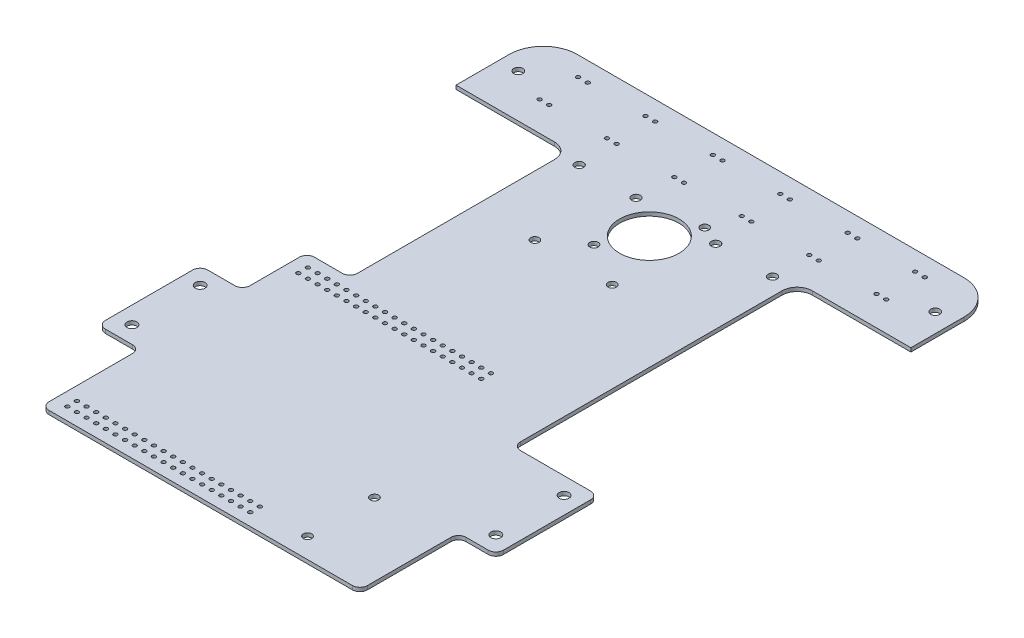
SolidWorks part; units mm, degrees
material "Thornel VCB-20 Carbon Cloth"
ref_plane "Front" through (0, 0, 0) normal (0, 0, 1) x (1, 0, 0)
ref_plane "Top" through (0, 0, 0) normal (0, 1, 0) x (1, 0, 0)
ref_plane "Right" through (0, 0, 0) normal (1, 0, 0) x (0, 0, -1)
ref_axis "X" through (-80.9, 0, 0) along (1, 0, 0)
ref_axis "Y" through (0, -50, 0) along (0, 1, 0)
ref_axis "Z" through (0, 0, -80.9) along (0, 0, 1)
sketch "Sketch1" plane through (0, 0, 0) normal (0, 1, 0) x (1, 0, 0)
  line L0 (-52.5, -125) -> (-41.35, -125)
  line L1 (-52.5, -125) -> (-52.5, -98)
  line L2 (-52.5, -98) -> (-41.35, -98)
  line L3 (-30, -81) -> (-30, -23)
  line L4 (-30, -23) -> (-60, -23)
  line L5 (-60, -23) -> (-60, 0)
  line L6 (-60, 0) -> (60, 0)
  line L7 (60, 0) -> (60, -23)
  line L8 (60, -23) -> (30, -23)
  line L9 (30, -23) -> (30, -98)
  line L10 (30, -98) -> (52.5, -98)
  line L11 (52.5, -98) -> (52.5, -125)
  line L12 (0, -162) -> (0, 0) construction
  line L13 (-41.35, -125) -> (-41.35, -151)
  line L14 (-41.35, -151) -> (42.65, -151)
  line L15 (42.65, -151) -> (42.65, -125)
  line L16 (42.65, -125) -> (52.5, -125)
  line L18 (-41.35, -98) -> (-41.35, -81)
  line L19 (-41.35, -81) -> (-30, -81)
  dimension "D1" = 105
  dimension "D2" = 60
  dimension "D3" = 27
  dimension "D4" = 90
  dimension "D5" = 23
  dimension "D6" = 120
  dimension "D7" = 125
  dimension "D8" = 41.35
  dimension "D9" = 26
  dimension "D10" = 42.65
  dimension "D11" = 17
extrude "Boss-Extrude1" add sketch "Sketch1" along normal mid plane 1
hole_wizard "M2 Clearance Hole1" positions "Sketch2" profile "Sketch3" hole size "M2" standard "ANSI Metric" end condition up to next
sketch "Sketch2" plane through (0, 0.5, 0) normal (0, 1, 0) x (1, 0, 0)
  line L0 (-48, -120.5) -> (48, -120.5) construction
  line L2 (-52.5, -125) -> (-41.35, -125) construction
  line L3 (-52.5, -98) -> (-52.5, -125) construction
  line L4 (52.5, -125) -> (52.5, -98) construction
  line L5 (-48, -102.5) -> (-48, -120.5) construction
  line L8 (48, -102.5) -> (48, -120.5) construction
  point P0 (-48, -120.5)
  point P2 (48, -120.5)
  point P15 (-48, -102.5)
  point P17 (48, -102.5)
  dimension "D1" = 4.5
  dimension "D2" = 4.5
  dimension "D3" = 4.5
  dimension "D4" = 18
sketch "Sketch3" plane through (-48, 0.5, 120.5) normal (1, 0, 0) x (0, 0, 1)
  line L0 (0, 0) -> (0, 1)
  line L1 (0, 1) -> (1.3, 1)
  line L2 (1.3, 1) -> (1.3, 0)
  line L5 (1.3, 0) -> (0, 0)
  line L11 (0, -6.35) -> (0, 107.95) construction
  dimension "Thru Hole Dia." = 2.6
  dimension "Thru Hole Depth" = 1
fillet "Fillet1" radius 2 7 edges at (-52.5, 0, 125) (52.5, 0, 98) (-52.5, 0, 98) (-41.35, 0, 151) (42.65, 0, 151) (52.5, 0, 125) (-41.35, 0, 81)
fillet "Fillet2" radius 9 2 edges at (60, 0, 0) (-60, 0, 0)
hole_wizard "M2 Clearance Hole2" positions "Sketch7" profile "Sketch8" hole size "M2" standard "ANSI Metric" end condition up to next
sketch "Sketch7" plane through (0, 0.5, 0) normal (0, 1, 0) x (1, 0, 0)
  line L0 (-55, -11.57) -> (55, -11.57) construction
  line L2 (0, 0) -> (0, -11.57) construction
  line L3 (51, 0) -> (-51, 0) construction
  line L5 (-60, -23) -> (-30, -23) construction
  point P0 (-55, -11.57)
  point P2 (55, -11.57)
  dimension "D1" = 110
  dimension "D2" = 11.43
sketch "Sketch8" plane through (-55, 0.5, 11.57) normal (1, 0, 0) x (0, 0, 1)
  line L0 (0, 0) -> (0, 1)
  line L1 (0, 1) -> (1.2, 1)
  line L2 (1.2, 1) -> (1.2, 0)
  line L5 (1.2, 0) -> (0, 0)
  line L11 (0, -6.35) -> (0, 107.95) construction
  dimension "Thru Hole Dia." = 2.4
  dimension "Thru Hole Depth" = 1
fillet "Fillet4" radius 2 5 edges at (30, 0, 98) (42.65, 0, 125) (-41.35, 0, 125) (-30, 0, 81) (-41.35, 0, 98)
fillet "Fillet5" radius 4 2 edges at (30, 0, 23) (-30, 0, 23)
sketch "Sketch13" plane through (0, 0.5, 0) normal (0, 1, 0) x (1, 0, 0)
  line L0 (-38, -106) -> (-38, -117) construction
  line L1 (-35, -106) -> (-35, -117)
  line L3 (38, -106) -> (38, -117) construction
  line L5 (35, -106) -> (35, -117)
  line L6 (-38, -111.5) -> (38, -111.5) construction
  line L7 (0, -111.5) -> (0, 0) construction
  line L8 (51, 0) -> (-51, 0) construction
  line L11 (-48, -102.5) -> (-48, -120.5) construction
  line L12 (-48, -111.5) -> (-38, -111.5) construction
  line L13 (-38, -103) -> (-45.5, -103)
  line L14 (-38, -120) -> (-45.5, -120)
  line L15 (38, -103) -> (45.5, -103)
  line L16 (38, -120) -> (45.5, -120)
  line L17 (48.5, -106) -> (48.5, -117)
  line L18 (-48.5, -106) -> (-48.5, -117)
  line L19 (-35, -111.5) -> (-48.5, -111.5) construction
  line L20 (35, -111.5) -> (48.5, -111.5) construction
  arc A0 (-35, -106) -> (-38, -103) centre (-38, -106) ccw
  arc A1 (-38, -120) -> (-35, -117) centre (-38, -117) ccw
  arc A2 (38, -103) -> (35, -106) centre (38, -106) ccw
  arc A3 (35, -117) -> (38, -120) centre (38, -117) ccw
  circle A4 centre (-48, -102.5) radius 1.3 construction
  arc A5 (45.5, -103) -> (48.5, -106) centre (45.5, -106) cw
  arc A6 (48.5, -117) -> (45.5, -120) centre (45.5, -117) cw
  arc A7 (-45.5, -103) -> (-48.5, -106) centre (-45.5, -106) ccw
  arc A8 (-48.5, -117) -> (-45.5, -120) centre (-45.5, -117) ccw
  point P2 (-38, -111.5)
  point P8 (38, -111.5)
  dimension "D5" = 3.5
  dimension "D1" = 17
  dimension "D2" = 13.5
  dimension "D3" = 70
extrude "Cut-Extrude4" [suppressed] cut sketch "Sketch13" against normal through all
hole_wizard "M2 Clearance Hole3" positions "Sketch14" profile "Sketch15" hole size "M2" standard "ANSI Metric" end condition up to next
sketch "Sketch14" plane through (0, 0.5, 0) normal (0, 1, 0) x (1, 0, 0)
  line L2 (5.35, -22.7335) -> (-5.35, -41.2665) construction
  line L3 (0, 0) -> (0, -32) construction
  line L4 (51, 0) -> (-51, 0) construction
  point P0 (5.35, -22.7335)
  point P2 (-5.35, -41.2665)
  dimension "D1" = 21.4
  dimension "D2" = 32
  dimension "D3" = 30
sketch "Sketch15" plane through (5.35, 0.5, 22.7335) normal (1, 0, 0) x (0, 0, 1)
  line L0 (0, 0) -> (0, 1)
  line L1 (0, 1) -> (1.1, 1)
  line L2 (1.1, 1) -> (1.1, 0)
  line L5 (1.1, 0) -> (0, 0)
  line L11 (0, -6.35) -> (0, 107.95) construction
  dimension "Thru Hole Dia." = 2.2
  dimension "Thru Hole Depth" = 1
sketch "Sketch17" plane through (0, 0.5, 0) normal (0, 1, 0) x (1, 0, 0)
  line L0 (-25.5, -25) -> (-10.5, -25) construction
  line L1 (-10.5, -25) -> (10.5, -25) construction
  line L2 (10.5, -25) -> (25.5, -25) construction
  line L4 (0, -25) -> (0, 0) construction
  line L5 (-18, -25) -> (-18, -29.652) construction
  line L7 (51, 0) -> (-51, 0) construction
  line L8 (18, -25) -> (18, -28.4507) construction
  circle A8 centre (25.5, -25) radius 1.15
  circle A9 centre (10.5, -25) radius 1.15
  circle A10 centre (-10.5, -25) radius 1.15
  circle A11 centre (-25.5, -25) radius 1.15
  dimension "D7" = 2.3
  dimension "D1" = 15
  dimension "D2" = 36
  dimension "D4" = 25
extrude "Cut-Extrude6" cut sketch "Sketch17" against normal through all
sketch "Sketch18" plane through (0, 0.5, 0) normal (0, 1, 0) x (1, 0, 0)
  line L0 (5.35, -22.7335) -> (-5.35, -41.2665) construction
  circle A0 centre (0, -32) radius 7.85
  circle A6 centre (5.35, -22.7335) radius 1.1 construction
  circle A8 centre (-5.35, -41.2665) radius 1.1 construction
  dimension "D3" = 15.7
extrude "Cut-Extrude7" cut sketch "Sketch18" against normal up to next
hole_wizard "M2 Clearance Hole4" positions "Sketch19" profile "Sketch20" hole size "M2" standard "ANSI Metric" end condition up to next
sketch "Sketch19" plane through (0, 0.5, 0) normal (0, 1, 0) x (1, 0, 0)
  line L0 (-14.21, -48) -> (6.21, -48) construction
  line L2 (0, 0) -> (0, -48) construction
  line L3 (51, 0) -> (-51, 0) construction
  point P0 (-14.21, -48)
  point P2 (6.21, -48)
  dimension "D1" = 20.42
  dimension "D2" = 6.21
  dimension "D3" = 48
sketch "Sketch20" plane through (-14.21, 0.5, 48) normal (1, 0, 0) x (0, 0, 1)
  line L0 (0, 0) -> (0, 1)
  line L1 (0, 1) -> (1.1, 1)
  line L2 (1.1, 1) -> (1.1, 0)
  line L5 (1.1, 0) -> (0, 0)
  line L11 (0, -6.35) -> (0, 107.95) construction
  dimension "Thru Hole Dia." = 2.2
  dimension "Thru Hole Depth" = 1
sketch "Sketch21" plane through (0, 0.5, 0) normal (0, 1, 0) x (1, 0, 0)
  line L0 (-37.826, -86.7798) -> (-37.826, -147.73) construction
  line L4 (-39.35, -151) -> (40.65, -151) construction
  line L5 (-41.35, -127) -> (-41.35, -149) construction
  circle A0 centre (-37.826, -147.73) radius 0.51
  circle A2 centre (-37.826, -86.7798) radius 0.51
  dimension "D2" = 1.02
  dimension "D3" = 3.524
  dimension "D4" = 3.27
  dimension "D1" = 60.9502
extrude "Cut-Extrude8" cut sketch "Sketch21" against normal up to next
pattern_linear "LPattern1" count 2 spacing 2.54 along (0, 0, -1) count 20 spacing 2.54 along (1, 0, 0) of "Cut-Extrude8"
sketch "Sketch22" plane through (0, 0.5, 0) normal (0, 1, 0) x (1, 0, 0)
  line L0 (-45.72, -5.08) -> (-43.18, -5.08) construction
  line L1 (51, 0) -> (-51, 0) construction
  line L2 (-44.45, -5.08) -> (-44.45, 0) construction
  circle A0 centre (-45.72, -5.08) radius 0.51
  circle A1 centre (-43.18, -5.08) radius 0.51
  point P8 (0, 0)
  dimension "D2" = 1.02
  dimension "D1" = 2.54
  dimension "D3" = 5.08
  dimension "D4" = 44.45
extrude "Cut-Extrude9" cut sketch "Sketch22" against normal up to next
pattern_linear "LPattern2" count 2 spacing 10.16 along (0, 0, 1) count 6 spacing 17.78 along (1, 0, 0) of "Cut-Extrude9"
sketch "Sketch23" plane through (0, 0.5, 0) normal (0, 1, 0) x (1, 0, 0)
  line L0 (42.65, -149) -> (42.65, -127) construction
  line L1 (-39.35, -151) -> (40.65, -151) construction
  circle A0 centre (23.48, -145.65) radius 1.1
  circle A1 centre (23.48, -128) radius 1.1
  point P4 (0, 0)
  dimension "D1" = 2.2
  dimension "D2" = 17.65
  dimension "D3" = 19.17
  dimension "D4" = 5.35
extrude "Cut-Extrude10" cut sketch "Sketch23" against normal through all
equation "\"dd\"=4"
